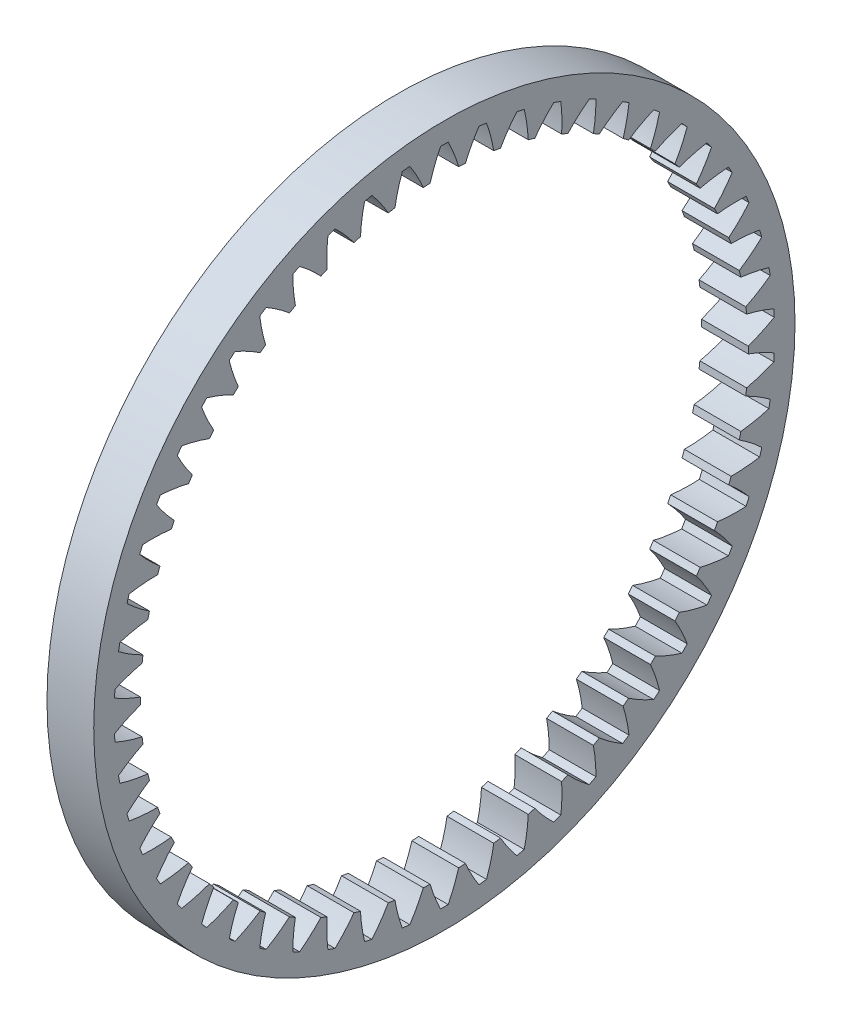
SolidWorks part; units mm, degrees
ref_plane "Plane1" through (0, 0, 0) normal (0, 0, 1) x (1, 0, 0)
ref_plane "Plane2" through (0, 0, 0) normal (0, 1, 0) x (1, 0, 0)
ref_plane "Plane3" through (0, 0, 0) normal (1, 0, 0) x (0, 0, -1)
sketch "HoldingSke" plane through (0, 0, 0) normal (0, 1, 0) x (1, 0, 0)
  line L0 (0, 0) -> (0.5878, -0.809)
  line L1 (-15, 0) -> (100, 0) construction
  line L2 (0, 0) -> (-2.1039, 2.3779)
  line L3 (0, 0) -> (-11.863, 4.5341)
  line L4 (0, 0) -> (5.0761, 6.9867)
  line L5 (0, 0) -> (-23.7986, -8.8762)
  line L6 (0, 0) -> (-10.5278, -7.1032)
  line L7 (-2.1039, 2.3779) -> (3.3635, 27.1825)
  line L8 (-76.2, 3.3779) -> (-54.61, 3.3779)
  line L9 (-71.009, 38.7566) -> (-53.1078, 45.2721)
  line L10 (-76.2, 71.12) -> (104.1128, 71.12)
  line L11 (0, 0) -> (-4, 0)
  line L12 (-76.2, 101.6) -> (-76.162, 101.6)
  line L13 (24.9733, 27.94) -> (52.9518, 28.4284)
  line L14 (24.9733, 27.94) -> (24.9743, 27.94)
  line L15 (24.9733, 27.94) -> (100.4006, 29.5858)
  circle A0 centre (0, 0) radius 30
  circle A1 centre (0, 0) radius 12.7
  circle A2 centre (0, 0) radius 12.7
  dimension "Num_teeth" = 54
  dimension "Pitch_radius" = 180.3128
  dimension "Width" = 4
  dimension "Diameter" = 60
sketch "BasProSke" plane through (0, 0, 0) normal (0, 1, 0) x (1, 0, 0)
  line L0 (-10, 0) -> (60, 0) construction
  line L1 (0, 26) -> (0, 30)
  line L2 (0, 26) -> (4, 26)
  line L3 (4, 26) -> (4, 30)
  line L4 (4, 30) -> (0, 30)
  dimension "Thickness" = 4
  dimension "Diameter" = 60
revolve "Base-Revolve" add sketch "BasProSke" angle 360 about L0
sketch "TooCutSke" plane through (0, 0, 0) normal (1, 0, 0) x (0, 0, -1)
  line L3 (0.8803, 26.9856) -> (0.8803, 53.6633) construction
  line L4 (0, 0) -> (0, 59.563) construction
  line L5 (0, 0) -> (-3.9729, 68.2119) construction
  line L6 (-11.739, 22.1895) -> (36.4511, 24.9963) construction
  circle A0 centre (0, 0) radius 27 construction
  circle A1 centre (0, 0) radius 28.251 construction
  circle A2 centre (0, 0) radius 22.8345 construction
  circle A3 centre (0, 0) radius 25.9746 construction
  arc A4 (1.2279, 25.9456) -> (0.3246, 28.2491) centre (-11.739, 22.1895) ccw
  arc A5 (1.2279, 25.9456) -> (-1.2279, 25.9456) centre (0, 0) ccw
  arc A6 (0.3246, 28.2491) -> (-0.3246, 28.2491) centre (0, 0) ccw
  arc A7 (-0.3246, 28.2491) -> (-1.2279, 25.9456) centre (11.739, 22.1895) ccw
extrude "ToothCut" cut sketch "TooCutSke" along normal through all
fillet "Breaks" [suppressed] radius 0.1
fillet "RootFillets" [suppressed] radius 0.251
pattern_circular "TeethCuts" count 54 every 6.667 about axis through (-10, 0, 0) along (1, 0, 0) of "RootFillets", "Breaks", "ToothCut"
ref_plane "基准面1" through (2, 0, 0) normal (1, 0, 0) x (0, 0, -1)
sketch "草图1" plane through (2, 0, 0) normal (1, 0, 0) x (0, 0, -1)
  line L0 (0, 0) -> (0, 28.251)
  line L1 (0, 0) -> (26, 0)
ref_plane "基准面2" through (0, 0, 0) normal (0, 0, -1) x (-1, 0, 0)
ref_plane "基准面3" through (0, 0, 0) normal (0, -1, 0) x (-1, 0, 0)
equation "' \"Module@HoldingSke\" = 6.35"
equation "' \"Num_teeth@HoldingSke\" = 24"
equation "' \"Ap@HoldingSke\" =  14.5"
equation "' \"Ap@HoldingSke\" = 14.5"
equation "' \"Width@HoldingSke\" = 12"
equation "' \"Diameter@HoldingSke\" = 8 * 25.4"
equation "' \"Show_teeth@HoldingSke\" = 100"
equation "' \"Backlash@HoldingSke\" = 0.009 * 25.4"
equation "' \"Addendum_fac@HoldingSke\" = 1.0"
equation "' \"Dedendum_fac@HoldingSke\" = 1.25"
equation "' \"Dedendum_add@HoldingSke\" = 0.00005 * 25.4"
equation "' \"Clearance_fac@HoldingSke\" = 0.25"
equation "\"Pitch@HoldingSke\" = 1 / \"Module@HoldingSke\" "
equation "\"Overcut_dia@TooCutSke\" = (\"Num_teeth@HoldingSke\" - 2 * \"Addendum_fac@HoldingSke\") / \"Pitch@HoldingSke\" - 0.002 * 25.4"
equation "\"Pitch_dia@TooCutSke\" = \"Num_teeth@HoldingSke\" / \"Pitch@HoldingSke\""
equation "\"Base_dia@TooCutSke\" = \"Num_teeth@HoldingSke\" / \"Pitch@HoldingSke\" * cos((\"Ap@HoldingSke\"  * 3.14159265 / 180)) * 0.90"
equation "\"Root_dia@TooCutSke\" = \"Num_teeth@HoldingSke\"  / \"Pitch@HoldingSke\" + 2 *  \"Dedendum_fac@HoldingSke\"/ \"Pitch@HoldingSke\" + \"Dedendum_add@HoldingSke\" * 2"
equation "\"Half_ang@TooCutSke\" = 180 / \"Num_teeth@HoldingSke\""
equation "\"Half_CT@TooCutSke\" = \"Num_teeth@HoldingSke\" / \"Pitch@HoldingSke\" * sin((3.14159265 / 2 / \"Num_teeth@HoldingSke\")) / 2 + 10 * \"Backlash@HoldingSke\" / 4"
equation "\"Flank_rad@TooCutSke\" = \"Num_teeth@HoldingSke\" / \"Pitch@HoldingSke\" / 4"
equation "\"Radius@RootFillets\"= \"Clearance_fac@HoldingSke\" / \"Pitch@HoldingSke\" + \"Dedendum_add@HoldingSke\""
equation "\"Break_rad@Breaks\" = 0.02 / \"Pitch@HoldingSke\" * 5"
equation "\"Num_teeth@TeethCuts\" = int( \"Show_teeth@HoldingSke\" ) + 1"
equation "\"Num_teeth@TeethCuts\" = ((sgn( \"Num_teeth@TeethCuts\" - \"Num_teeth@HoldingSke\" )-1)*( \"Num_teeth@TeethCuts\" - \"Num_teeth@HoldingSke\" ))/-2+ \"Num_teeth@HoldingSke\""
equation "\"Num_teeth@TeethCuts\" = ((sgn( \"Num_teeth@TeethCuts\" - 2.0)+1)*( \"Num_teeth@TeethCuts\" - 2.0))/2 +2.0"
equation "\"Angle@TeethCuts\" = 360.0 / \"Num_teeth@HoldingSke\""
equation "\"Diameter@BasProSke\" = \"Num_teeth@HoldingSke\"  / \"Pitch@HoldingSke\" + 2 *  \"Dedendum_fac@HoldingSke\"/ \"Pitch@HoldingSke\" + \"Dedendum_add@HoldingSke\" * 2 + 0.002 * 25.4"
equation "\"Diameter@BasProSke\" = ((sgn( \"Diameter@BasProSke\"  - \"Diameter@HoldingSke\" )+1)*( \"Diameter@BasProSke\"  - \"Diameter@HoldingSke\" ))/2 + \"Diameter@HoldingSke\""
equation "\"Inside_diameter@BasProSke\" =  (\"Num_teeth@HoldingSke\" - 2 * \"Addendum_fac@HoldingSke\") / \"Pitch@HoldingSke\" "
equation "\"Thickness@BasProSke\"  = \"Width@HoldingSke\""
